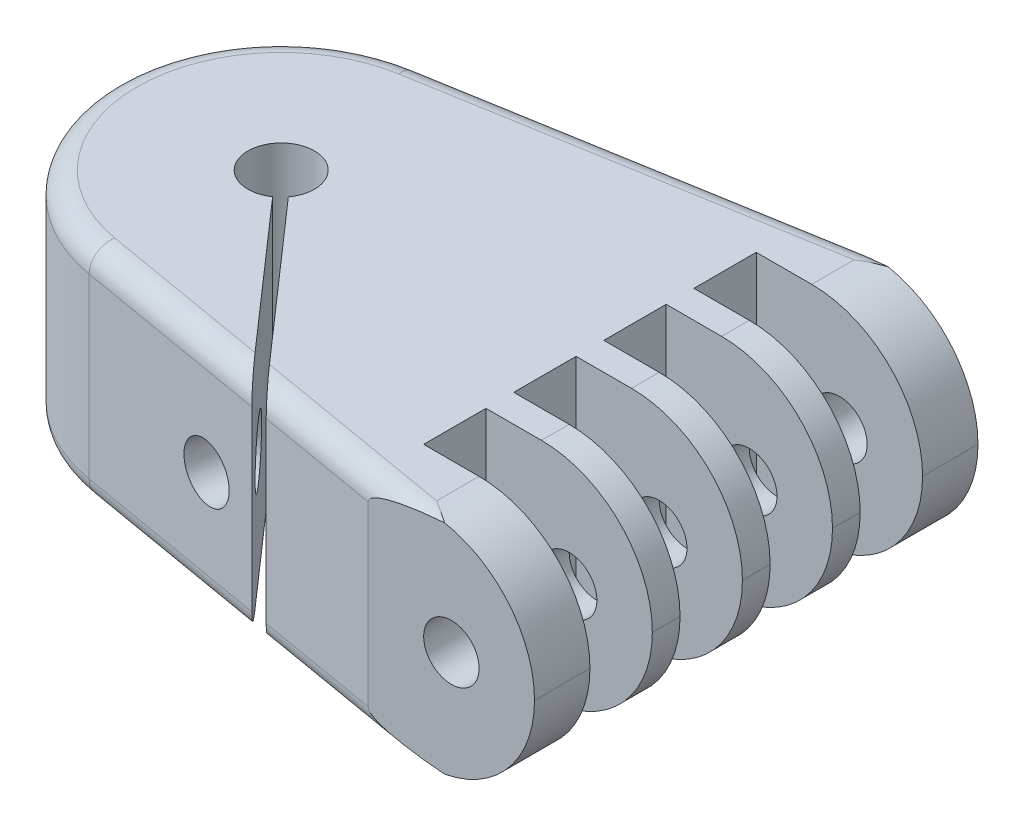
SolidWorks part; units mm, degrees
ref_plane "Front Plane" through (0, 0, 0) normal (0, 0, 1) x (1, 0, 0)
ref_plane "Top Plane" through (0, 0, 0) normal (0, 1, 0) x (1, 0, 0)
ref_plane "Right Plane" through (0, 0, 0) normal (1, 0, 0) x (0, 0, -1)
sketch "Sketch1" plane through (0, 0, 0) normal (0, 1, 0) x (1, 0, 0)
  line L0 (27.8497, 15) -> (27.8497, 9.375)
  line L1 (-2.5377, 14.7838) -> (27.8497, 20)
  line L2 (-2.5377, -14.7838) -> (15.1764, -17.8245)
  line L3 (27.8497, 20) -> (42.8497, 20)
  line L4 (42.8497, 20) -> (42.8497, 15)
  line L5 (42.8497, -20) -> (27.8497, -20)
  line L6 (42.8497, 15) -> (27.8497, 15)
  line L7 (27.8497, 1.25) -> (42.8497, 1.25)
  line L8 (27.8497, -1.25) -> (42.8497, -1.25)
  line L9 (27.8497, -6.875) -> (42.8497, -6.875)
  line L10 (27.8497, -9.375) -> (42.8497, -9.375)
  line L11 (27.8497, -15) -> (42.8497, -15)
  line L12 (27.8497, 9.375) -> (42.8497, 9.375)
  line L13 (42.8497, 6.875) -> (27.8497, 6.875)
  line L14 (42.8497, 9.375) -> (42.8497, 6.875)
  line L15 (42.8497, 1.25) -> (42.8497, -1.25)
  line L16 (42.8497, -6.875) -> (42.8497, -9.375)
  line L17 (42.8497, -15) -> (42.8497, -20)
  line L18 (7.0698, -7.0724) -> (16.743, -18.0935)
  line L19 (6.3182, -7.732) -> (15.1764, -17.8245)
  line L20 (6.3182, -7.732) -> (15.9915, -18.7531) construction
  line L21 (16.743, -18.0935) -> (27.8497, -20)
  line L22 (27.8497, 6.875) -> (27.8497, 1.25)
  line L23 (27.8497, -1.25) -> (27.8497, -6.875)
  line L24 (27.8497, -9.375) -> (27.8497, -15)
  arc A0 (7.0698, -7.0724) -> (6.328, -7.7432) centre (0, 0) ccw
  arc A1 (-2.5377, 14.7838) -> (-2.5377, -14.7838) centre (0, 0) ccw
  dimension "D1" = 20
  dimension "D2" = 30
  dimension "D3" = 40
  dimension "D4" = 5
  dimension "D5" = 2.5
  dimension "D6" = 2.5
  dimension "D7" = 5
  dimension "D8" = 2.5
  dimension "D9" = 5.625
  dimension "D10" = 5.625
  dimension "D11" = 5.625
  dimension "D12" = 1
  dimension "D13" = 15
extrude "Boss-Extrude1" add sketch "Sketch1" along normal blind 20 contours L1 A1 L2 L19 A0 L18 L21 L5 L17 L11 L24 L10 L16 L9 L23 L8 L15 L7 L22 L13 L14 L12 L0 L6 L4 L3 region at (16.6641, 0, -0.1403)
fillet "Fillet1" radius 10 10 edges at (42.8497, 0, 17.5) (42.8497, 0, 8.125) (42.8497, 0, 0) (42.8497, 0, -8.125) (42.8497, 0, -17.5) (42.8497, 20, -17.5) (42.8497, 20, -8.125) (42.8497, 20, 0) (42.8497, 20, 8.125) (42.8497, 20, 17.5)
sketch "Sketch2" plane through (0, 0, -20) normal (0, 0, -1) x (-1, 0, 0)
  circle A0 centre (-35.3497, 10) radius 2.5
  dimension "D1" = 5
  dimension "D2" = 7.5
extrude "Cut-Extrude1" cut sketch "Sketch2" against normal blind 40
fillet "Fillet2" radius 2 8 edges at (12.656, 0, -17.3919) (6.3193, 0, 16.3042) (12.656, 20, -17.3919) (6.3193, 20, 16.3042) (22.2964, 0, 19.0467) (22.2964, 20, 19.0467) (-15, 0, 0) (-15, 20, 0)
sketch "Sketch3" plane through (-2.5377, 0, 14.7838) normal (-0.1692, 0, 0.9856) x (0.9856, 0, 0.1692)
  line L0 (17.9733, 18) -> (17.9733, 2) construction
  circle A0 centre (12.9733, 10) radius 2.5
  dimension "D1" = 5
  dimension "D2" = 5
extrude "Cut-Extrude2" cut sketch "Sketch3" against normal blind 10
sketch "Sketch4" plane through (0, 0, 0) normal (0, -1, 0) x (1, 0, 0)
  circle A0 centre (0, 0) radius 10
  circle A1 centre (0, 0) radius 3
  dimension "D1" = 6
extrude "Boss-Extrude2" add sketch "Sketch4" against normal up to surface (20 mm away) up to face at (23.4922, 20, 1.2971)
sketch "Sketch6" plane through (0, 0, 0) normal (0, -1, 0) x (1, 0, 0)
  line L0 (6.328, 7.7432) -> (1.7008, 2.4713)
  line L1 (6.328, 7.7432) -> (13.0794, 15.4353) construction
  line L2 (7.0698, 7.0724) -> (2.4193, 1.774)
  line L3 (7.0698, 7.0724) -> (14.646, 15.7042) construction
  circle A0 centre (0, 0) radius 3 construction
  arc A1 (7.0698, 7.0724) -> (6.328, 7.7432) centre (0, 0) ccw construction
  arc A2 (7.0698, 7.0724) -> (6.328, 7.7432) centre (0, 0) ccw
  circle A3 centre (0, 0) radius 3
  arc M6 (7.0698, 7.0724) -> (6.328, 7.7432) centre (0, 0) ccw
  circle M27 centre (0, 0) radius 3
extrude "Cut-Extrude3" cut sketch "Sketch6" against normal through all contours L2 L0 M6 M27 region at (4.3918, 0, 4.7786)
